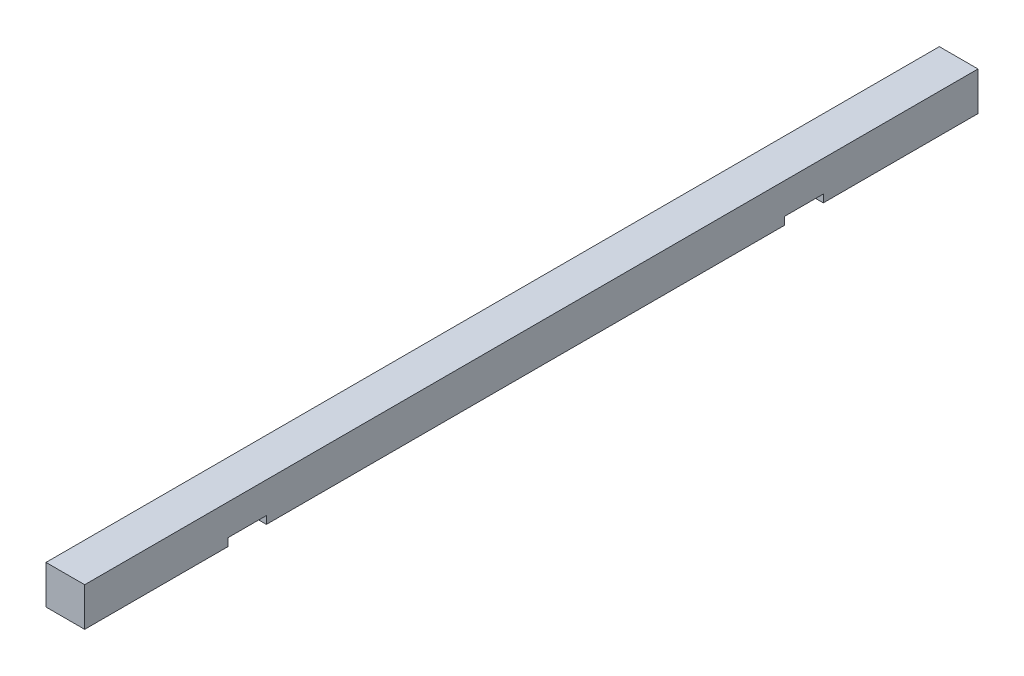
SolidWorks part; units mm, degrees
ref_plane "Plan de face" through (0, 0, 0) normal (0, 0, 1) x (1, 0, 0)
ref_plane "Plan de dessus" through (0, 0, 0) normal (0, 1, 0) x (1, 0, 0)
ref_plane "Plan de droite" through (0, 0, 0) normal (1, 0, 0) x (0, 0, -1)
sketch "Esquisse1" plane through (0, 0, 0) normal (0, 0, 1) x (1, 0, 0)
  line L1 (0, 0) -> (10, 0)
  line L2 (0, 0) -> (0, 10)
  line L3 (0, 10) -> (10, 10)
  line L4 (10, 0) -> (10, 10)
  dimension "D1" = 10
  dimension "D2" = 10
extrude "Boss.-Extru.1" add sketch "Esquisse1" along normal blind 231
sketch "Esquisse2" plane through (0, 0, 0) normal (0, -1, 0) x (1, 0, 0)
  line L0 (0, 231) -> (0, 0) construction
  line L1 (0, 184) -> (10, 184)
  line L2 (0, 184) -> (0, 194)
  line L3 (0, 194) -> (10, 194)
  line L4 (10, 184) -> (10, 194)
  line L5 (10, 231) -> (10, 0) construction
  line L6 (0, 231) -> (10, 231) construction
  point P10 (5, 231)
  dimension "D1" = 10
  dimension "D2" = 37
extrude "Enlèv. mat.-Extru.1" cut sketch "Esquisse2" against normal blind 2
sketch "Esquisse3" plane through (0, 0, 0) normal (0, -1, 0) x (1, 0, 0)
  line L0 (0, 184) -> (0, 0) construction
  line L1 (0, 40) -> (10, 40)
  line L2 (0, 40) -> (0, 50)
  line L3 (0, 50) -> (10, 50)
  line L4 (10, 40) -> (10, 50)
  line L5 (10, 184) -> (10, 0) construction
  line L6 (0, 0) -> (10, 0) construction
  point P10 (5, 0)
  dimension "D1" = 10
  dimension "D2" = 40
extrude "Enlèv. mat.-Extru.2" cut sketch "Esquisse3" against normal blind 2
